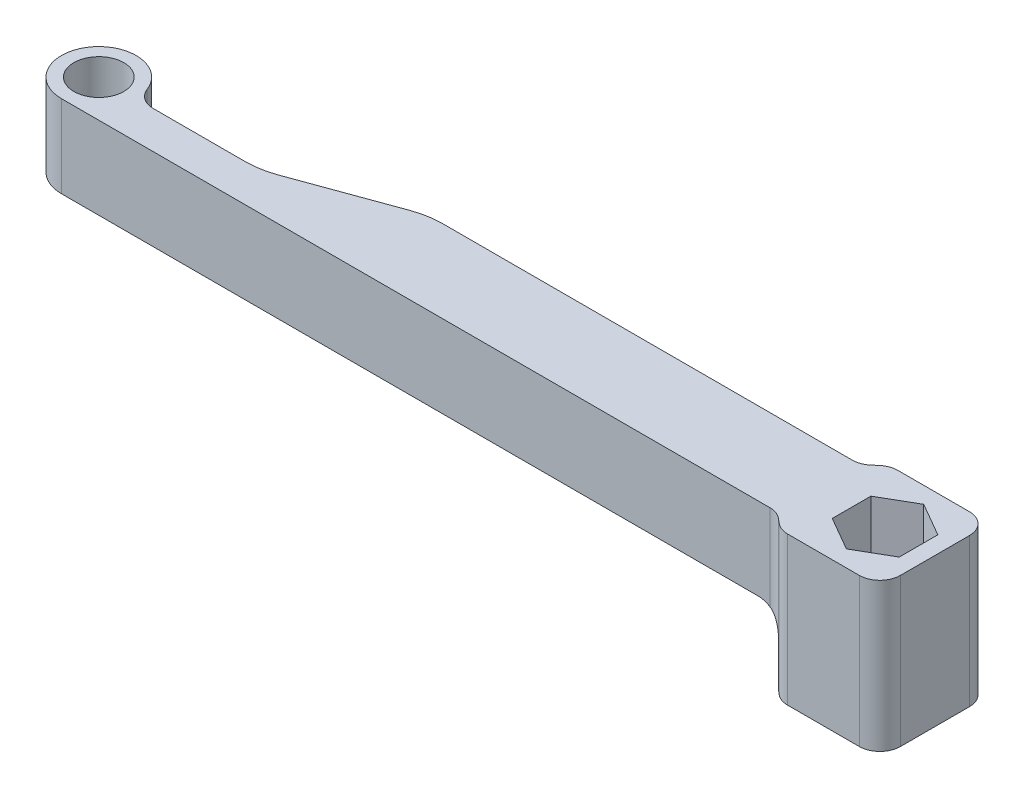
SolidWorks part; units mm, degrees
ref_plane "Front Plane" through (0, 0, 0) normal (0, 0, 1) x (1, 0, 0)
ref_plane "Top Plane" through (0, 0, 0) normal (0, 1, 0) x (1, 0, 0)
ref_plane "Right Plane" through (0, 0, 0) normal (1, 0, 0) x (0, 0, -1)
sketch "Sketch1" plane through (0, 0, 0) normal (0, 1, 0) x (1, 0, 0)
  line L0 (0, 6.075) -> (0, 9.075) construction
  line L1 (9.075, 0) -> (39.075, 0)
  line L3 (0, -9.075) -> (200, -9.075)
  line L7 (39.075, 0) -> (69.0912, 10.925)
  line L8 (9.075, 0) -> (0, 0) construction
  line L9 (200, -9.075) -> (200, 0)
  line L10 (69.0912, 10.925) -> (200, 10.925)
  line L11 (200, 10.925) -> (200, 0)
  circle A0 centre (0, 0) radius 6.075
  circle A1 centre (0, 0) radius 9.075 construction
  arc A6 (9.075, 0) -> (0, -9.075) centre (0, 0) ccw
  dimension "D1" = 12.15
  dimension "D2" = 3
  dimension "D3" = 200
  dimension "D4" = 20
  dimension "D5" = 30
  dimension "D6" = 20
extrude "Boss-Extrude1" add sketch "Sketch1" along normal blind 20
sketch "Sketch5" plane through (0, 20, 0) normal (0, 1, 0) x (1, 0, 0)
  line L0 (190, 0.925) -> (190, -9.075) construction
  line L1 (190, 10.3098) -> (181.8725, 5.6174)
  line L2 (181.8725, 5.6174) -> (181.8725, -3.7674)
  line L3 (181.8725, -3.7674) -> (190, -8.4598)
  line L4 (190, -8.4598) -> (198.1275, -3.7674)
  line L5 (198.1275, -3.7674) -> (198.1275, 5.6174)
  line L6 (198.1275, 5.6174) -> (190, 10.3098)
  line L7 (0, -9.075) -> (200, -9.075) construction
  line L8 (190, 10.925) -> (190, 0.925) construction
  line L9 (200, 10.925) -> (69.0912, 10.925) construction
  line L10 (190, 0.925) -> (200, 0.925) construction
  line L11 (200, -9.075) -> (200, 10.925) construction
  circle A0 centre (190, 0.925) radius 8.1275 construction
  point P18 (200, 0.925)
  dimension "D1" = 16.255
extrude "Cut-Extrude3" cut sketch "Sketch5" against normal through all both and the other way through all
sketch "Sketch6" plane through (0, 20, 0) normal (0, 1, 0) x (1, 0, 0)
  line L0 (200, -9.075) -> (200, 10.925) construction
  line L7 (0, -9.075) -> (200, -9.075) construction
  line L8 (181.8725, 5.6174) -> (181.8725, -3.7674) construction
  line L9 (173.8725, 10.925) -> (177.9064, 14.3098)
  line L10 (177.9064, 14.3098) -> (202.1275, 14.3098)
  line L11 (202.1275, 14.3098) -> (202.1275, -12.4598)
  line L12 (173.8725, 10.925) -> (200, 10.925)
  line L13 (200, 10.925) -> (200, -9.075)
  line L14 (200, 0.925) -> (202.1275, 0.925) construction
  line L15 (173.8725, -9.075) -> (200, -9.075)
  line L16 (177.9064, -12.4598) -> (202.1275, -12.4598)
  line L17 (173.8725, -9.075) -> (177.9064, -12.4598)
  line L18 (198.1275, -3.7674) -> (198.1275, 5.6174) construction
  dimension "D1" = 8
  dimension "D2" = 4
  dimension "D3" = 4
  dimension "D4" = 40
extrude "Boss-Extrude2" add sketch "Sketch6" against normal up to surface (20 mm away) up to face at (190, 0, -0.925)
sketch "Sketch7" plane through (0, 0, 0) normal (0, -1, 0) x (1, 0, 0)
  line L0 (173.8725, 9.075) -> (173.8725, -10.925)
  line L7 (198.1275, -5.6174) -> (198.1275, 3.7674)
  line L8 (190, -10.3098) -> (198.1275, -5.6174)
  line L9 (69.0912, -10.925) -> (173.8725, -10.925)
  line L10 (173.8725, -10.925) -> (177.9064, -14.3098)
  line L11 (177.9064, -14.3098) -> (202.1275, -14.3098)
  line L12 (202.1275, -14.3098) -> (202.1275, 12.4598)
  line L13 (202.1275, 12.4598) -> (177.9064, 12.4598)
  line L14 (177.9064, 12.4598) -> (173.8725, 9.075)
  line L15 (173.8725, 9.075) -> (0, 9.075)
  line L16 (9.075, 0) -> (39.075, 0)
  line L17 (39.075, 0) -> (69.0912, -10.925)
  line L19 (173.8725, -10.925) -> (177.9064, -14.3098)
  line L20 (177.9064, -14.3098) -> (202.1275, -14.3098)
  line L21 (202.1275, -14.3098) -> (202.1275, 12.4598)
  line L22 (202.1275, 12.4598) -> (177.9064, 12.4598)
  line L23 (177.9064, 12.4598) -> (173.8725, 9.075)
  line L27 (181.8725, -5.6174) -> (190, -10.3098)
  line L28 (181.8725, 3.7674) -> (181.8725, -5.6174)
  line L29 (190, 8.4598) -> (181.8725, 3.7674)
  line L30 (198.1275, 3.7674) -> (190, 8.4598)
  line L31 (198.1275, -5.6174) -> (198.1275, 3.7674)
  line L32 (190, -10.3098) -> (198.1275, -5.6174)
  line L33 (181.8725, -5.6174) -> (190, -10.3098)
  line L34 (181.8725, 3.7674) -> (181.8725, -5.6174)
  line L35 (190, 8.4598) -> (181.8725, 3.7674)
  line L36 (198.1275, 3.7674) -> (190, 8.4598)
  arc A1 (0, 9.075) -> (9.075, 0) centre (0, 0) ccw
  dimension "D1" = 0
  dimension "D2" = 0
extrude "Boss-Extrude3" add sketch "Sketch7" along normal offset from surface (12 mm away) 32 up to face at (121.4099, 20, -1.8354)
sketch "Sketch8" plane through (0, -12, 0) normal (0, -1, 0) x (1, 0, 0)
  line L6 (177.9064, -14.3098) -> (202.1275, -14.3098)
  line L7 (202.1275, -14.3098) -> (202.1275, 12.4598)
  line L8 (202.1275, 12.4598) -> (177.9064, 12.4598)
  line L9 (177.9064, 12.4598) -> (173.8725, 9.075)
  line L10 (173.8725, 9.075) -> (173.8725, -10.925)
  line L11 (173.8725, -10.925) -> (177.9064, -14.3098)
  line L12 (177.9064, -14.3098) -> (202.1275, -14.3098)
  line L13 (202.1275, -14.3098) -> (202.1275, 12.4598)
  line L14 (202.1275, 12.4598) -> (177.9064, 12.4598)
  line L15 (177.9064, 12.4598) -> (173.8725, 9.075)
  line L16 (173.8725, 9.075) -> (173.8725, -10.925)
  line L17 (173.8725, -10.925) -> (177.9064, -14.3098)
  dimension "D1" = 0
extrude "Boss-Extrude4" add sketch "Sketch8" along normal blind 4
fillet "Fillet1" radius 5 6 edges at (202.1275, 2, 12.4598) (202.1275, 2, -14.3098) (173.8725, -8, 9.075) (173.8725, -8, -10.925) (177.9064, 2, -14.3098) (177.9064, 2, 12.4598)
fillet "Fillet2" radius 5 3 edges at (174.341, 0, 8.8566) (174.341, 0, -10.7066) (173.8725, 0, -0.925)
fillet "Fillet3" radius 5 2 edges at (173.8725, 8.607, -10.925) (173.8725, 8.607, 9.075)
fillet "Fillet4" radius 20 2 edges at (69.0912, 10, -10.925) (39.075, 10, 0)
fillet "Fillet5" radius 5 1 edges at (9.075, 10, 0)
sketch "Sketch9" plane through (0, 20, 0) normal (0, 1, 0) x (1, 0, 0)
  line L0 (-9.0749, -0.0415) -> (202.1275, 0.925) construction
  line L1 (202.1275, -7.4598) -> (202.1275, 9.3098) construction
  arc A0 (8.4831, 3.2238) -> (0, -9.075) centre (0, 0) ccw construction
